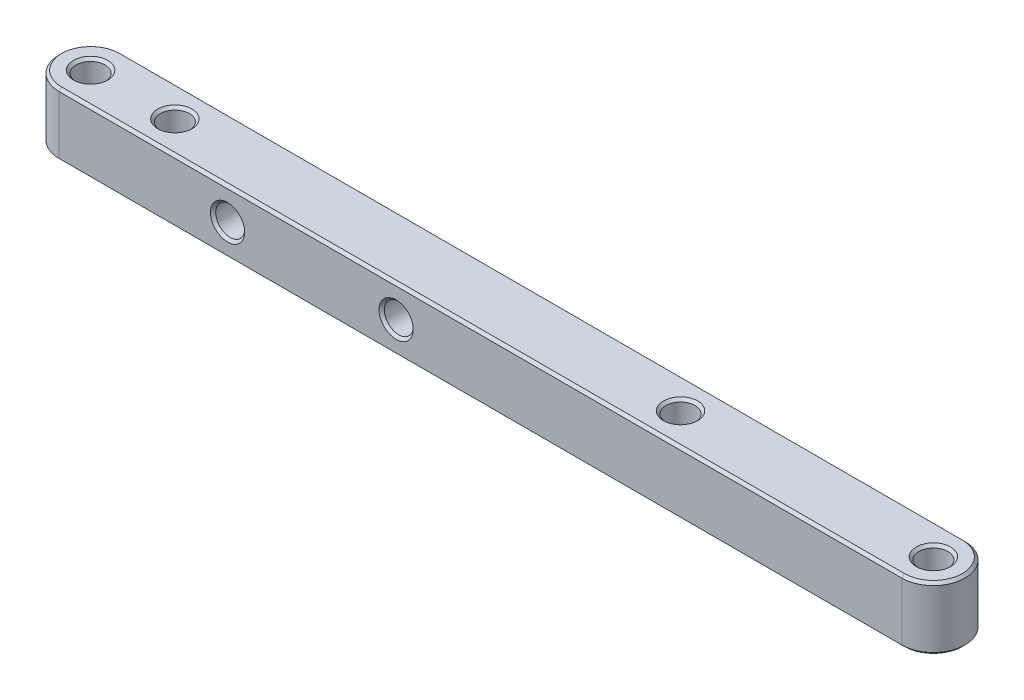
SolidWorks part; units mm, degrees
ref_plane "Front Plane" through (0, 0, 0) normal (0, 0, 1) x (1, 0, 0)
ref_plane "Top Plane" through (0, 0, 0) normal (0, 1, 0) x (1, 0, 0)
ref_plane "Right Plane" through (0, 0, 0) normal (1, 0, 0) x (0, 0, -1)
sketch "Sketch1" plane through (0, 0, 0) normal (0, 1, 0) x (1, 0, 0)
  line L0 (0, 0) -> (127, 0) construction
  line L1 (0, 4.7625) -> (127, 4.7625)
  line L2 (0, -4.7625) -> (127, -4.7625)
  arc A0 (0, 4.7625) -> (0, -4.7625) centre (0, 0) ccw
  arc A1 (127, -4.7625) -> (127, 4.7625) centre (127, 0) ccw
  circle A2 centre (0, 0) radius 2.1828
  circle A3 centre (12.7, 0) radius 2.1828
  circle A4 centre (127, 0) radius 2.1828
  circle A5 centre (88.9, 0) radius 2.1828
  point P3 (63.5, 0)
  dimension "D2" = 4.7625
  dimension "D4" = 4.3656
  dimension "D5" = 4.3656
  dimension "D6" = 4.3656
  dimension "D8" = 4.3656
  dimension "D1" = 127
  dimension "D3" = 12.7
  dimension "D7" = 38.1
extrude "Boss-Extrude1" add sketch "Sketch1" along normal blind 9.525
sketch "Sketch2" plane through (0, 0, 4.7625) normal (0, 0, 1) x (1, 0, 0)
  circle A0 centre (25.4, 4.7625) radius 2.1828
  circle A1 centre (50.8, 4.7625) radius 2.1828
  point P4 (0, 0)
  dimension "D4" = 4.3656
  dimension "D5" = 4.3656
  dimension "D1" = 4.7625
  dimension "D2" = 25.4
  dimension "D3" = 25.4
extrude "Cut-Extrude1" cut sketch "Sketch2" against normal through all both and the other way through all
chamfer "Chamfer1" distance 0.3969 angle 45 20 edges at (23.2172, 4.7625, 4.7625) (27.5828, 4.7625, -4.7625) (48.6172, 4.7625, 4.7625) (52.9828, 4.7625, -4.7625) (88.9, 0, 2.1828) (127, 0, 2.1828) (12.7, 0, 2.1828) (0, 0, 2.1828) (63.5, 0, 4.7625) (131.7625, 0, 0) (63.5, 0, -4.7625) (-4.7625, 0, 0) (88.9, 9.525, 2.1828) (12.7, 9.525, 2.1828) (63.5, 9.525, -4.7625) (131.7625, 9.525, 0) (63.5, 9.525, 4.7625) (-4.7625, 9.525, 0) (0, 9.525, 2.1828) (127, 9.525, 2.1828)
